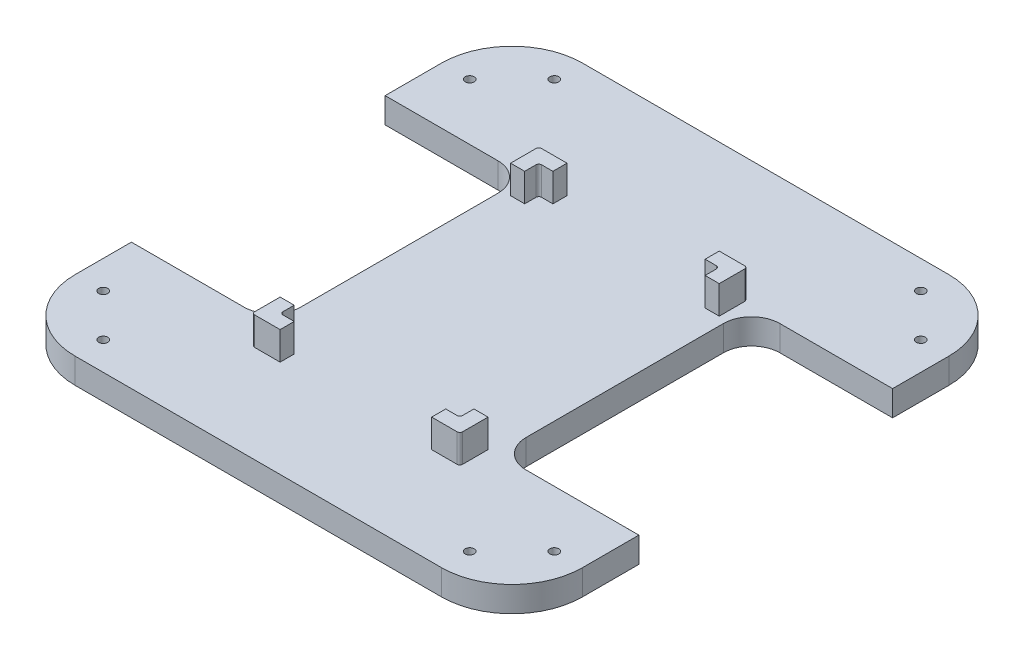
SolidWorks part; units mm, degrees
ref_plane "Front Plane" through (0, 0, 0) normal (0, 0, 1) x (1, 0, 0)
ref_plane "Top Plane" through (0, 0, 0) normal (0, 1, 0) x (1, 0, 0)
ref_plane "Right Plane" through (0, 0, 0) normal (1, 0, 0) x (0, 0, -1)
sketch "Sketch1" plane through (0, 0, 0) normal (0, 1, 0) x (1, 0, 0)
  line L1 (-65, -90) -> (65, -90)
  line L2 (-90, -65) -> (-90, 65)
  line L3 (-65, 90) -> (65, 90)
  line L4 (90, -65) -> (90, 65)
  arc A0 (-90, 65) -> (-65, 90) centre (-65, 65) cw
  arc A1 (65, 90) -> (90, 65) centre (65, 65) cw
  arc A2 (90, -65) -> (65, -90) centre (65, -65) cw
  arc A3 (-65, -90) -> (-90, -65) centre (-65, -65) cw
  point P4 (-90, 0)
  point P6 (0, 90)
  dimension "D3" = 25
  dimension "D1" = 180
  dimension "D2" = 180
extrude "Plate" add sketch "Sketch1" along normal blind 9
sketch "Sketch3" plane through (0, 9, 0) normal (0, 1, 0) x (1, 0, 0)
  line L0 (-65, 90) -> (-65, -90) construction
  line L1 (65, 90) -> (65, -90) construction
  line L2 (-90, 65) -> (90, 65) construction
  line L3 (-90, -65) -> (90, -65) construction
  circle A0 centre (-65, 80) radius 1.6
  circle A1 centre (-80, 65) radius 1.6
  circle A2 centre (80, 65) radius 1.6
  circle A3 centre (80, -65) radius 1.6
  circle A4 centre (65, 80) radius 1.6
  circle A5 centre (65, -80) radius 1.6
  circle A6 centre (-65, -80) radius 1.6
  circle A7 centre (-80, -65) radius 1.6
  dimension "D1" = 3.2
  dimension "D2" = 15
  dimension "D3" = 15
  dimension "D4" = 15
  dimension "D5" = 15
  dimension "D6" = 15
  dimension "D7" = 15
  dimension "D8" = 15
  dimension "D9" = 15
extrude "Hex Holes" cut sketch "Sketch3" against normal through all
sketch "Sketch4" plane through (0, 9, 0) normal (0, 1, 0) x (1, 0, 0)
  line L0 (0, 90) -> (0, -90) construction
  line L1 (-65, 90) -> (65, 90) construction
  line L2 (-65, -90) -> (65, -90) construction
  line L3 (-32, 36.5) -> (-32, 41.5)
  line L4 (-31.5, 41) -> (31.5, 41) construction
  line L5 (-31.5, 41) -> (-31.5, -50) construction
  line L6 (-31.5, -50) -> (31.5, -50) construction
  line L7 (31.5, 41) -> (31.5, -50) construction
  line L8 (-32, 41.5) -> (-27, 41.5)
  line L9 (-27, 41.5) -> (-27, 46.5)
  line L10 (-27, 46.5) -> (-37, 46.5)
  line L11 (-37, 46.5) -> (-37, 36.5)
  line L12 (-37, 36.5) -> (-32, 36.5)
  line L13 (27, 46.5) -> (37, 46.5)
  line L14 (37, 46.5) -> (37, 36.5)
  line L15 (37, 36.5) -> (32, 36.5)
  line L16 (32, 36.5) -> (32, 41.5)
  line L17 (32, 41.5) -> (27, 41.5)
  line L18 (27, 41.5) -> (27, 46.5)
  line L19 (-36.75, -45.5) -> (-36.75, -55.5)
  line L20 (-36.75, -55.5) -> (-26.75, -55.5)
  line L21 (-26.75, -55.5) -> (-26.75, -50.5)
  line L22 (-26.75, -50.5) -> (-31.75, -50.5)
  line L23 (-31.75, -50.5) -> (-31.75, -45.5)
  line L24 (-31.75, -45.5) -> (-36.75, -45.5)
  line L25 (27, -50.5) -> (27, -55.5)
  line L26 (27, -55.5) -> (37, -55.5)
  line L27 (37, -55.5) -> (37, -45.5)
  line L28 (37, -45.5) -> (32, -45.5)
  line L29 (32, -45.5) -> (32, -50.5)
  line L30 (32, -50.5) -> (27, -50.5)
  point P10 (0, 41)
  point P25 (-37, 41.5)
  dimension "D1" = 91
  dimension "D2" = 63
  dimension "D3" = 40
  dimension "D4" = 0.5
  dimension "D5" = 0.5
  dimension "D6" = 5
  dimension "D7" = 0.5
  dimension "D8" = 0.5
  dimension "D9" = 0.5
  dimension "D10" = 0.5
  dimension "D11" = 0.5
extrude "Raspberry Pi Holder" add sketch "Sketch4" along normal blind 10
fillet "Fillet1" radius 1 8 edges at (-37, 14, -46.5) (-32, 14, -41.5) (-31.75, 14, 50.5) (-36.75, 14, 55.5) (32, 14, 50.5) (37, 14, 55.5) (37, 14, -46.5) (32, 14, -41.5)
sketch "Sketch5" plane through (0, 9, 0) normal (0, 1, 0) x (1, 0, 0)
  line L0 (-90, -65) -> (-90, 65) construction
  line L1 (-90, 45) -> (-40, 45)
  line L2 (-90, 45) -> (-90, -45)
  line L3 (-90, -45) -> (-40, -45)
  line L4 (-40, 45) -> (-40, -45)
  line L5 (90, -65) -> (90, 65) construction
  line L6 (90, 45) -> (40, 45)
  line L7 (90, 45) -> (90, -45)
  line L8 (90, -45) -> (40, -45)
  line L9 (40, 45) -> (40, -45)
  point P12 (-90, 0)
  point P14 (90, 0)
  dimension "D1" = 90
  dimension "D2" = 50
extrude "Cut-Extrude1" cut sketch "Sketch5" against normal through all
fillet "Fillet2" radius 10 4 edges at (-40, 4.5, 45) (40, 4.5, 45) (40, 4.5, -45) (-40, 4.5, -45)
